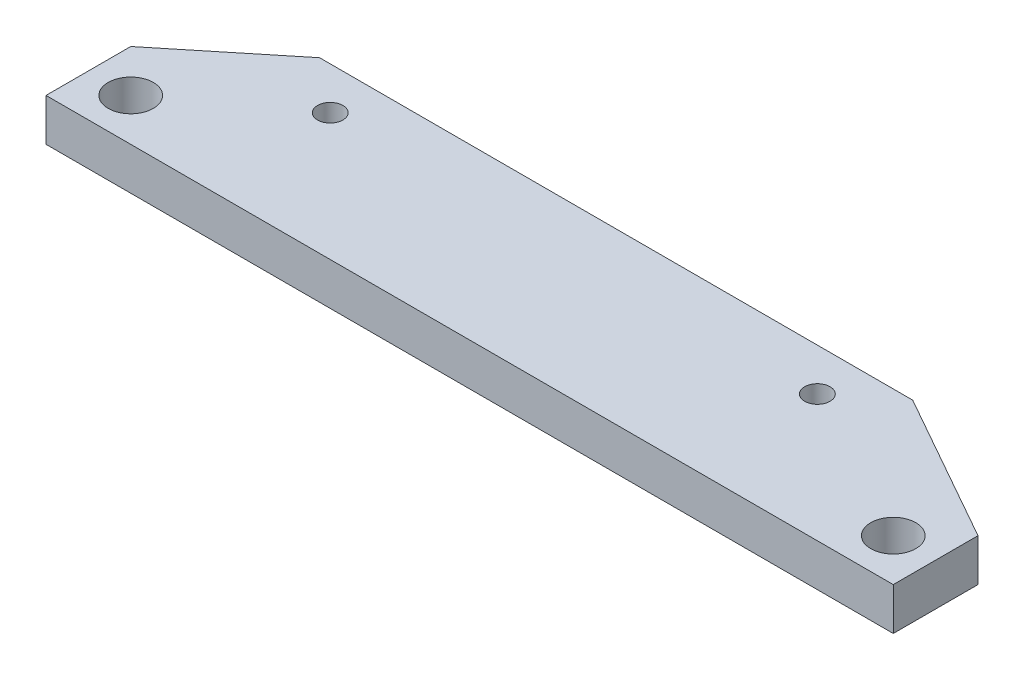
SolidWorks part; units mm, degrees
ref_plane "Front Plane" through (0, 0, 0) normal (0, 0, 1) x (1, 0, 0)
ref_plane "Top Plane" through (0, 0, 0) normal (0, 1, 0) x (1, 0, 0)
ref_plane "Right Plane" through (0, 0, 0) normal (1, 0, 0) x (0, 0, -1)
sketch "Sketch8" plane through (0, 0, 0) normal (0, 1, 0) x (1, 0, 0)
  line L0 (44.45, 0) -> (44.45, -12.7)
  line L1 (0, 0) -> (88.9, 0)
  line L2 (0, 0) -> (0, -12.7)
  line L3 (0, -12.7) -> (88.9, -12.7)
  line L4 (88.9, 0) -> (88.9, -12.7)
  line L5 (7.9375, -6.35) -> (80.9625, -6.35)
  line L7 (0, 0) -> (-15.6113, -12.7)
  line L8 (-15.6113, -12.7) -> (111.3887, -12.7)
  line L9 (-15.6113, -12.7) -> (-15.6113, -25.4)
  line L10 (-15.6113, -25.4) -> (111.3887, -25.4)
  line L11 (111.3887, -12.7) -> (111.3887, -25.4)
  line L12 (-15.6113, -12.7) -> (111.3887, -25.4) construction
  line L13 (-15.6113, -25.4) -> (111.3887, -12.7) construction
  line L14 (88.9, 0) -> (111.3887, -12.7)
  line L15 (105.0387, -19.05) -> (-9.2613, -19.05)
  point P10 (44.45, -6.35)
  point P11 (43.1744, -19.05)
  point P15 (45.8354, -19.05)
  point P16 (45.7845, -19.05)
  point P23 (47.8887, -19.05)
  dimension "D1" = 12.7
  dimension "D2" = 88.9
  dimension "D3" = 73.025
  dimension "D4" = 12.7
  dimension "D5" = 127
  dimension "D6" = 0
  dimension "D7" = 114.3
extrude "Boss-Extrude3" add sketch "Sketch8" along normal blind 6.35 contours L7 L8 L3 L2 | L14 L4 L3 L8 | L9 L8 L11 L10 | L2 L1 L4 L3 region at (-5.2038, 0, 8.4667) region at (96.3962, 0, 8.4667)
hole_wizard "CBORE for #6 Socket Head Cap Screw1" positions "Sketch11" profile "Sketch12" counterbore size "#6" standard "ANSI Inch" end condition up to next
sketch "Sketch11" plane through (0, 0, 0) normal (0, -1, 0) x (-1, 0, 0)
  point P0 (-80.9625, -6.35)
  point P3 (-7.9375, -6.35)
sketch "Sketch12" plane through (80.9625, 0, 6.35) normal (1, 0, 0) x (0, 0, -1)
  line L0 (0, 0) -> (0, 6.35)
  line L1 (0, 6.35) -> (1.8986, 6.35)
  line L3 (1.8986, 6.35) -> (1.8986, 3.5052)
  line L4 (1.8986, 3.5052) -> (3.5725, 3.5052)
  line L5 (3.5725, 3.5052) -> (3.5725, 0)
  line L7 (3.5725, 0) -> (0, 0)
  line L11 (0, -6.35) -> (0, 107.95) construction
  dimension "Thru Hole Dia." = 3.7973
  dimension "Thru Hole Depth" = 6.35
  dimension "C'Bore Dia." = 7.145
  dimension "C'Bore Depth" = 3.5052
hole_wizard "1/4 Clearance Hole1" positions "Sketch13" profile "Sketch14" hole size "1/4" standard "ANSI Inch" end condition up to next
sketch "Sketch13" plane through (0, 6.35, 0) normal (0, 1, 0) x (1, 0, 0)
  point P0 (-9.2613, -19.05)
  point P3 (105.0387, -19.05)
sketch "Sketch14" plane through (-9.2613, 6.35, 19.05) normal (1, 0, 0) x (0, 0, 1)
  line L0 (0, 0) -> (0, 6.35)
  line L1 (0, 6.35) -> (3.3782, 6.35)
  line L2 (3.3782, 6.35) -> (3.3782, 0)
  line L5 (3.3782, 0) -> (0, 0)
  line L11 (0, -6.35) -> (0, 107.95) construction
  dimension "Thru Hole Dia." = 6.7564
  dimension "Thru Hole Depth" = 6.35
ref_axis "Axis1" through (-9.2613, 0, 19.05) along (0, 1, 0)
ref_axis "Axis2" through (105.0387, 0, 19.05) along (0, 1, 0)
sketch "Sketch15" plane through (0, 0, 25.4) normal (0, 0, 1) x (1, 0, 0)
  line L0 (111.3887, 6.35) -> (111.3887, 0) construction
  line L1 (-15.6113, 6.35) -> (-15.6113, 0) construction
  line L2 (-15.6113, 6.35) -> (111.3887, 6.35) construction
  line L3 (-15.6113, 0) -> (111.3887, 0) construction
  line L4 (111.3887, 6.35) -> (111.3887, 0)
  line L5 (-15.6113, 6.35) -> (-15.6113, 0)
  line L6 (-15.6113, 6.35) -> (111.3887, 6.35)
  line L7 (-15.6113, 0) -> (111.3887, 0)
extrude "Cut-Extrude1" [suppressed] cut sketch "Sketch15" against normal blind 6.35
